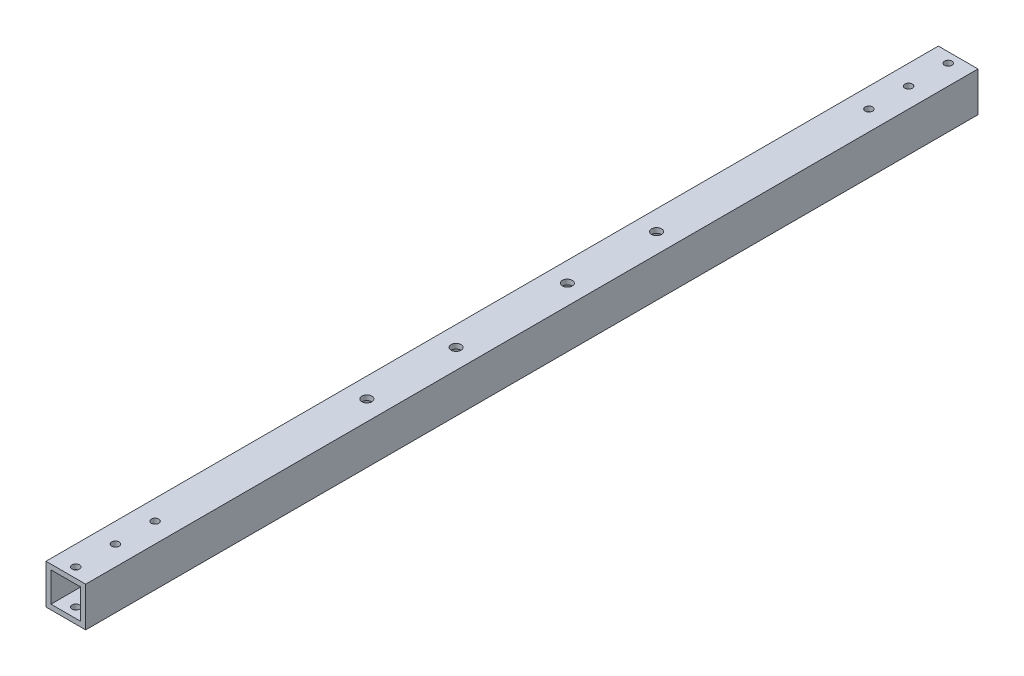
SolidWorks part; units mm, degrees
material "6061-T6 (SS)"
ref_plane "Front Plane" through (0, 0, 0) normal (0, 0, 1) x (1, 0, 0)
ref_plane "Top Plane" through (0, 0, 0) normal (0, 1, 0) x (1, 0, 0)
ref_plane "Right Plane" through (0, 0, 0) normal (1, 0, 0) x (0, 0, -1)
sketch "Sketch1" plane through (0, 0, 0) normal (0, 0, 1) x (1, 0, 0)
  line L1 (-12.7, -12.7) -> (12.7, -12.7)
  line L2 (-12.7, -12.7) -> (-12.7, 12.7)
  line L3 (-12.7, 12.7) -> (12.7, 12.7)
  line L4 (12.7, -12.7) -> (12.7, 12.7)
  line L5 (-12.7, -12.7) -> (12.7, 12.7) construction
  line L6 (-12.7, 12.7) -> (12.7, -12.7) construction
  point P0 (0, 0)
  dimension "D1" = 25.4
  dimension "D2" = 25.4
extrude "Extrude-Thin1" add sketch "Sketch1" along normal blind 571.5 thin thin type one direction reverse wall 3.175
hole_wizard "3/16 (0.1875) Diameter Hole1" positions "3DSketch1" profile "Sketch3" hole size "3/16" standard "ANSI Inch" end condition through all
sketch3d "3DSketch1"
  line L1 (12.7, 12.7, 0) -> (-12.7, 12.7, 0) construction
  line L6 (0, 12.7, 571.5) -> (0, 12.7, 0) construction
  line L7 (12.7, 12.7, 571.5) -> (-12.7, 12.7, 571.5) construction
  point P57 (0, 12.7, 6.35)
  point P59 (0, 12.7, 31.75)
  point P61 (0, 12.7, 57.15)
  point P63 (0, 12.7, 539.75)
  point P65 (0, 12.7, 514.35)
  point P67 (0, 12.7, 565.15)
  dimension "D1" = 25.4
  dimension "D2" = 25.4
  dimension "D3" = 6.35
  dimension "D4" = 25.4
  dimension "D5" = 25.4
  dimension "D6" = 6.35
sketch "Sketch3" plane through (0, 12.7, 565.15) normal (1, 0, 0) x (0, 0, 1)
  line L0 (0, 0) -> (0, 25.4)
  line L1 (0, 25.4) -> (2.3812, 25.4)
  line L2 (2.3812, 25.4) -> (2.3812, 0)
  line L5 (2.3812, 0) -> (0, 0)
  line L11 (0, -6.35) -> (0, 107.95) construction
  dimension "Thru Hole Dia." = 4.7625
  dimension "Thru Hole Depth" = 25.4
hole_wizard "1/4 (0.25) Diameter Hole1" positions "Sketch6" profile "Sketch7" hole size "1/4" standard "ANSI Inch" end condition through all
sketch "Sketch6" plane through (0, 12.7, 0) normal (0, 1, 0) x (1, 0, 0)
  point P0 (0, -321.564)
  point P3 (0, -378.714)
  point P6 (0, -193.167)
  point P9 (0, -250.317)
sketch "Sketch7" plane through (0, 12.7, 321.564) normal (1, 0, 0) x (0, 0, 1)
  line L0 (0, 0) -> (0, 25.4)
  line L1 (0, 25.4) -> (3.175, 25.4)
  line L2 (3.175, 25.4) -> (3.175, 0)
  line L5 (3.175, 0) -> (0, 0)
  line L11 (0, -6.35) -> (0, 107.95) construction
  dimension "Thru Hole Dia." = 6.35
  dimension "Thru Hole Depth" = 25.4
